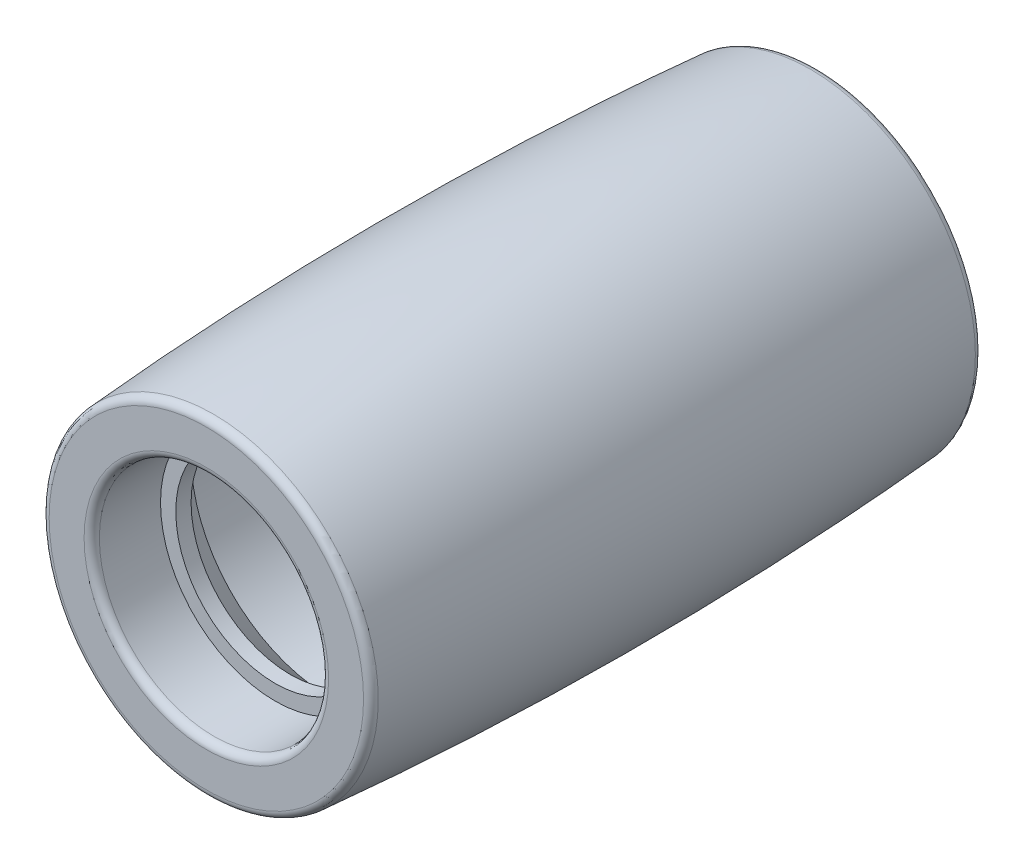
SolidWorks part; units mm, degrees
ref_plane "Ebene vorne" through (0, 0, 0) normal (0, 0, 1) x (1, 0, 0)
ref_plane "Ebene oben" through (0, 0, 0) normal (0, 1, 0) x (1, 0, 0)
ref_plane "Ebene rechts" through (0, 0, 0) normal (1, 0, 0) x (0, 0, -1)
sketch "Skizze1" plane through (0, 0, 0) normal (1, 0, 0) x (0, 0, -1)
  line L27 (0, 0) -> (99, 0) construction
  line L28 (89.5, 21.5) -> (89.5, 19.25) construction
  line L29 (81, 18.25) -> (83.1445, 19.25) construction
  line L30 (83.1445, 19.25) -> (89.5, 19.25) construction
  line L31 (42.3, 18.25) -> (81, 18.25) construction
  line L32 (42.3, 18.25) -> (42.3, 11) construction
  line L33 (42.3, 11) -> (39.3, 11) construction
  line L34 (39.3, 11) -> (39.3, 18.25) construction
  line L35 (20.5, 18.25) -> (39.3, 18.25) construction
  line L36 (20.5, 13) -> (27.7121, 20.2121) construction
  line L37 (18.5, 13) -> (20.5, 13) construction
  line L38 (18.5, 15) -> (18.5, 5) construction
  line L39 (18.5, 15) -> (9.5, 15) construction
  line L40 (9.5, 21.5) -> (9.5, 15) construction
  line L41 (0, 0) -> (99, 0) construction
  line L42 (89.5, 21.5) -> (89.5, 19.25)
  line L43 (81, 18.25) -> (83.1445, 19.25)
  line L44 (83.1445, 19.25) -> (89.5, 19.25)
  line L45 (42.3, 18.25) -> (81, 18.25)
  line L46 (42.3, 18.25) -> (42.3, 11)
  line L47 (42.3, 11) -> (39.3, 11)
  line L48 (39.3, 11) -> (39.3, 18.25)
  line L49 (25.75, 18.25) -> (39.3, 18.25)
  line L50 (20.5, 13) -> (25.75, 18.25)
  line L51 (18.5, 13) -> (20.5, 13)
  line L52 (18.5, 15) -> (18.5, 13)
  line L53 (18.5, 15) -> (9.5, 15)
  line L54 (9.5, 21.5) -> (9.5, 15)
  arc A2 (89.5, 21.5) -> (9.5, 21.5) centre (49.5, -511.0833) ccw construction
  arc A3 (89.5, 21.5) -> (9.5, 21.5) centre (49.5, -511.0833) ccw
revolve "Rotation1" add sketch "Skizze1" angle 360 about L27
sketch "Skizze4" plane through (0, 0, -39.3) normal (0, 0, 1) x (1, 0, 0)
  circle A0 centre (0, 0) radius 14 construction
  point P4 (0, 14)
hole_wizard "Durchgangsloch für M31" positions "Skizze4" profile "Skizze5" hole size "M3" standard "DIN"
sketch "Skizze5" plane through (0, 14, -39.3) normal (1, 0, 0) x (0, -1, 0)
  line L0 (0, 0) -> (0, 10.5815)
  line L1 (0, 10.5815) -> (1.8, 9.5)
  line L2 (1.8, 9.5) -> (1.8, 0)
  line L5 (1.8, 0) -> (0, 0)
  line L10 (0, 10.5815) -> (-1.8, 9.5) construction
  line L11 (0, -6.35) -> (0, 107.95) construction
  dimension "Bohrerdurchmesser" = 3.6
  dimension "Bohrungstiefe" = 9.5
  dimension "Spitzenwinkel" = 118
pattern_circular "Kreismuster2" count 4 over 360 of "Durchgangsloch für M31"
fillet "Verrundung1" radius 1 3 edges at (21.5, 0, -89.5) (21.5, 0, -9.5) (15, 0, -9.5)
